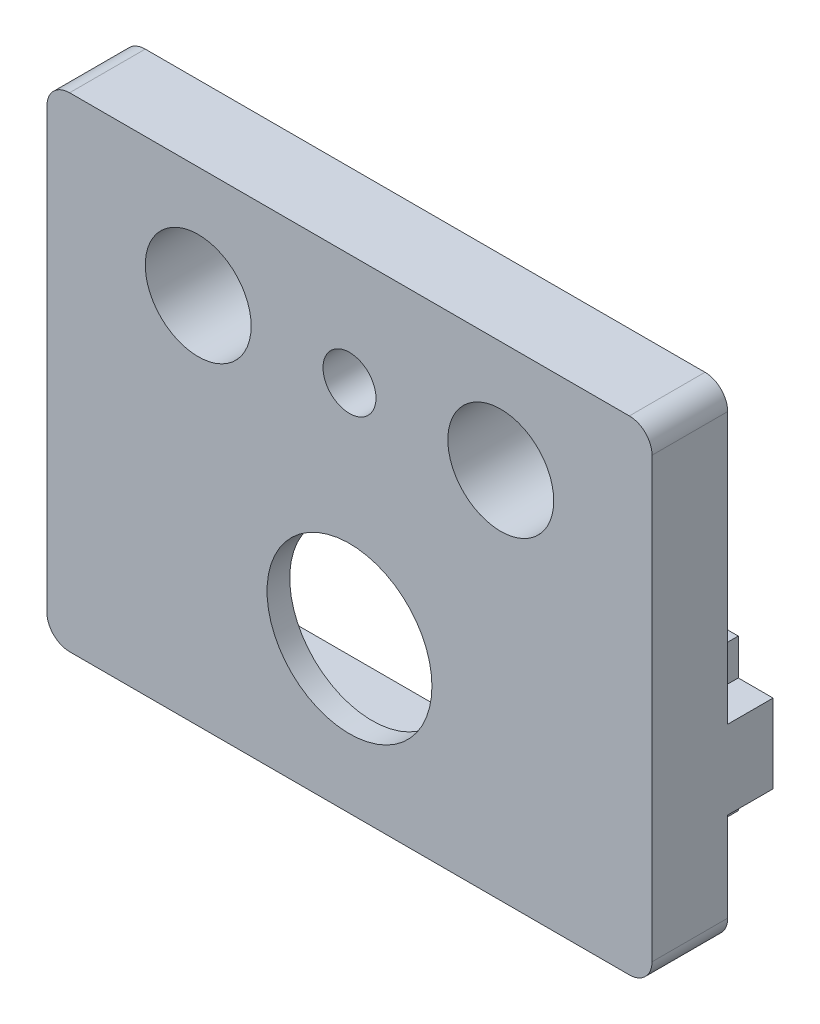
SolidWorks part; units mm, degrees
ref_plane "前视基准面" through (0, 0, 0) normal (0, 0, 1) x (1, 0, 0)
ref_plane "上视基准面" through (0, 0, 0) normal (0, 1, 0) x (1, 0, 0)
ref_plane "右视基准面" through (0, 0, 0) normal (1, 0, 0) x (0, 0, -1)
sketch "草图1" plane through (0, 0, 0) normal (0, 0, 1) x (1, 0, 0)
  line L1 (-9.5, -5.75) -> (9.5, -5.75)
  line L3 (-9.5, 5.75) -> (9.5, 5.75)
  line L5 (-20, -10) -> (20, -10)
  line L6 (-20, -10) -> (-20, 10)
  line L11 (-20, 10) -> (20, 10)
  line L12 (20, -10) -> (20, 10)
  line L13 (-20, -10) -> (20, 10) construction
  line L14 (-20, 10) -> (20, -10) construction
  arc A0 (9.5, -5.75) -> (9.5, 5.75) centre (-0.7708, 0) ccw
  arc A1 (-9.5, -5.75) -> (-9.5, 5.75) centre (0.7708, 0) cw
  point P0 (0, 0)
  point P6 (0, 0)
  point P7 (0, 0)
extrude "凸台-拉伸1" add sketch "草图1" along normal blind 3.5
sketch "草图2" plane through (0, 0, 3.5) normal (0, 0, 1) x (1, 0, 0)
  line L4 (20, -10) -> (20, 10)
  line L5 (20, 10) -> (-20, 10)
  line L6 (-20, 10) -> (-20, -10)
  line L7 (-20, -10) -> (20, -10)
  line L8 (20, -10) -> (20, 10)
  line L9 (20, 10) -> (-20, 10)
  line L10 (-20, 10) -> (-20, -10)
  line L11 (-20, -10) -> (20, -10)
  circle A0 centre (0, 0) radius 5.25
  dimension "D1" = 0
extrude "凸台-拉伸2" add sketch "草图2" along normal blind 1.5
sketch "草图3" plane through (0, 0, 5) normal (0, 0, 1) x (1, 0, 0)
  line L9 (-16.5607, 5.5) -> (-18.2, 5.5)
  line L13 (-13.9, -2.8393) -> (-13.9, 2.8393)
  line L19 (-16.5607, 5.5) -> (-13.9, 2.8393)
  line L22 (-18.2, 3.1) -> (-18.2, 5.5)
  line L23 (-18.2, 3.1) -> (-20, 3.1)
  line L24 (-18.2, -3.1) -> (-20, -3.1)
  line L25 (-18.2, -3.1) -> (-18.2, -5.5)
  line L28 (-16.5607, -5.5) -> (-13.9, -2.8393)
  line L32 (-16.5607, -5.5) -> (-18.2, -5.5)
  line L41 (18.2, 3.1) -> (20, 3.1)
  line L45 (18.2, 3.1) -> (18.2, 5.5)
  line L48 (16.5607, 5.5) -> (13.9, 2.8393)
  line L54 (13.9, -2.8393) -> (13.9, 2.8393)
  line L56 (16.5607, 5.5) -> (18.2, 5.5)
  line L63 (16.5607, -5.5) -> (18.2, -5.5)
  line L67 (16.5607, -5.5) -> (13.9, -2.8393)
  line L70 (18.2, -3.1) -> (18.2, -5.5)
  line L74 (18.2, -3.1) -> (20, -3.1)
  line L88 (-20, 3.1) -> (-20, -3.1)
  line L90 (20, 3.1) -> (20, -3.1)
  point P0 (-10, 0)
  point P8 (-10, 8.2)
  point P9 (-9.8043, 8.2)
  point P13 (-10, 8.2)
  point P20 (-5, 5)
  point P33 (-15, 5)
  point P50 (-15, -5)
  point P51 (-5, -5)
  point P52 (-10, -8.2)
  point P53 (-9.8043, -8.2)
  point P54 (10, 0)
  point P58 (10, 8.2)
  point P59 (10.1957, 8.2)
  point P63 (10, 8.2)
  point P70 (15, 5)
  point P83 (5, 5)
  point P102 (5, -5)
  point P103 (15, -5)
  point P104 (10, -8.2)
  point P105 (10.1957, -8.2)
extrude "凸台-拉伸3" add sketch "草图3" against normal blind 8
sketch "草图4" plane through (0, 0, 5) normal (0, 0, 1) x (1, 0, 0)
  line L3 (-20, 10) -> (-20, -10) construction
  line L6 (20, 10) -> (-20, 10)
  line L8 (-20, 10) -> (-20, 22)
  line L9 (-20, 22) -> (20, 22)
  line L10 (20, 22) -> (20, 10)
  circle A2 centre (-10, 14.64) radius 3.5
  circle A3 centre (10, 14.64) radius 3.5
  line M15 (20, 10) -> (-20, 10)
extrude "凸台-拉伸4" add sketch "草图4" against normal blind 5 contours L10 L9 L8 M15 region at (0, 16.2597, 5)
fillet "圆角1" radius 1.5 4 edges at (-20, 22, 2.5) (20, 22, 2.5) (20, -10, 2.5) (-20, -10, 2.5)
sketch "草图5" plane through (0, 0, 5) normal (0, 0, 1) x (1, 0, 0)
  circle A0 centre (0, 14.64) radius 1.75
extrude "切除-拉伸1" cut sketch "草图5" against normal blind 5
sketch "草图6" plane through (0, 0, -3) normal (0, 0, -1) x (-1, 0, 0)
  line L0 (-18.2, 5.5) -> (-18.2, 3.1) construction
  line L1 (-18.2, 3.1) -> (-20, 3.1) construction
  line L2 (-20, 3.1) -> (-20, -3.1) construction
  line L3 (-20, -3.1) -> (-18.2, -3.1) construction
  line L4 (-18.2, -3.1) -> (-18.2, -5.5) construction
  line L5 (-18.2, -5.5) -> (-16.5607, -5.5) construction
  line L6 (-16.5607, -5.5) -> (-13.9, -2.8393) construction
  line L7 (-13.9, -2.8393) -> (-13.9, 2.8393) construction
  line L8 (-13.9, 2.8393) -> (-16.5607, 5.5) construction
  line L9 (-16.5607, 5.5) -> (-18.2, 5.5) construction
  line L10 (18.2, -5.5) -> (18.2, -3.1) construction
  line L11 (18.2, -3.1) -> (20, -3.1) construction
  line L12 (20, -3.1) -> (20, 3.1) construction
  line L13 (20, 3.1) -> (18.2, 3.1) construction
  line L14 (18.2, 3.1) -> (18.2, 5.5) construction
  line L15 (18.2, 5.5) -> (16.5607, 5.5) construction
  line L16 (16.5607, 5.5) -> (13.9, 2.8393) construction
  line L17 (13.9, 2.8393) -> (13.9, -2.8393) construction
  line L18 (13.9, -2.8393) -> (16.5607, -5.5) construction
  line L19 (16.5607, -5.5) -> (18.2, -5.5) construction
  line L20 (-18.2, 5.5) -> (-18.2, 3.1)
  line L21 (-18.2, 3.1) -> (-20, 3.1)
  line L22 (-20, 3.1) -> (-20, 2.6)
  line L23 (-20, -3.1) -> (-18.2, -3.1)
  line L24 (-18.2, -3.1) -> (-18.2, -5.5)
  line L25 (-18.2, -5.5) -> (-16.5607, -5.5)
  line L26 (-16.5607, -5.5) -> (-13.9, -2.8393)
  line L27 (-13.9, -2.8393) -> (-13.9, 2.8393)
  line L28 (-13.9, 2.8393) -> (-16.5607, 5.5)
  line L29 (-16.5607, 5.5) -> (-18.2, 5.5)
  line L30 (18.2, -5.5) -> (18.2, -3.1)
  line L31 (18.2, -3.1) -> (20, -3.1)
  line L32 (20, -3.1) -> (20, -2.6)
  line L33 (20, 3.1) -> (18.2, 3.1)
  line L34 (18.2, 3.1) -> (18.2, 5.5)
  line L35 (18.2, 5.5) -> (16.5607, 5.5)
  line L36 (16.5607, 5.5) -> (13.9, 2.8393)
  line L37 (13.9, 2.8393) -> (13.9, -2.8393)
  line L38 (13.9, -2.8393) -> (16.5607, -5.5)
  line L39 (16.5607, -5.5) -> (18.2, -5.5)
  line L40 (-20, -2.6) -> (-20, -3.1)
  line L41 (19.5, -2.6) -> (20, -2.6)
  line L42 (19.5, 2.6) -> (20, 2.6)
  line L43 (20, 2.6) -> (20, 3.1)
  line L70 (-17.7, 5) -> (-17.7, 2.6)
  line L71 (-17.7, 2.6) -> (-19.5, 2.6)
  line L72 (-19.5, 2.6) -> (-19.5, -2.6)
  line L73 (-19.5, -2.6) -> (-17.7, -2.6)
  line L74 (-17.7, -2.6) -> (-17.7, -5)
  line L75 (-17.7, -5) -> (-16.7678, -5)
  line L76 (-16.7678, -5) -> (-14.4, -2.6322)
  line L77 (-14.4, -2.6322) -> (-14.4, 2.6322)
  line L78 (-14.4, 2.6322) -> (-16.7678, 5)
  line L79 (-16.7678, 5) -> (-17.7, 5)
  line L80 (-17.7, 5) -> (-17.7, 2.6)
  line L81 (-17.7, 2.6) -> (-19.5, 2.6)
  line L83 (-19.5, -2.6) -> (-17.7, -2.6)
  line L84 (-17.7, -2.6) -> (-17.7, -5)
  line L85 (-17.7, -5) -> (-16.7678, -5)
  line L86 (-16.7678, -5) -> (-14.4, -2.6322)
  line L87 (-14.4, -2.6322) -> (-14.4, 2.6322)
  line L88 (-14.4, 2.6322) -> (-16.7678, 5)
  line L89 (-16.7678, 5) -> (-17.7, 5)
  line L90 (-19.5, -2.6) -> (-20, -2.6)
  line L91 (-19.5, 2.6) -> (-20, 2.6)
  line L100 (17.7, -5) -> (17.7, -2.6)
  line L101 (17.7, -2.6) -> (19.5, -2.6)
  line L102 (19.5, -2.6) -> (19.5, 2.6)
  line L103 (19.5, 2.6) -> (17.7, 2.6)
  line L104 (17.7, 2.6) -> (17.7, 5)
  line L105 (17.7, 5) -> (16.7678, 5)
  line L106 (16.7678, 5) -> (14.4, 2.6322)
  line L107 (14.4, 2.6322) -> (14.4, -2.6322)
  line L108 (14.4, -2.6322) -> (16.7678, -5)
  line L109 (16.7678, -5) -> (17.7, -5)
  line L110 (17.7, -5) -> (17.7, -2.6)
  line L111 (17.7, -2.6) -> (19.5, -2.6)
  line L113 (19.5, 2.6) -> (17.7, 2.6)
  line L114 (17.7, 2.6) -> (17.7, 5)
  line L115 (17.7, 5) -> (16.7678, 5)
  line L116 (16.7678, 5) -> (14.4, 2.6322)
  line L117 (14.4, 2.6322) -> (14.4, -2.6322)
  line L118 (14.4, -2.6322) -> (16.7678, -5)
  line L119 (16.7678, -5) -> (17.7, -5)
  dimension "D1" = 0.5
  dimension "D2" = 0.5
extrude "切除-拉伸2" cut sketch "草图6" against normal blind 3
sketch "草图7" plane through (0, 0, 0) normal (0, 0, -1) x (-1, 0, 0)
  line L4 (9.6166, 5.95) -> (-9.6166, 5.95)
  line L5 (-9.6166, -5.95) -> (9.6166, -5.95)
  line L6 (9.6166, 5.95) -> (-9.6166, 5.95)
  line L7 (-9.6166, -5.95) -> (9.6166, -5.95)
  arc A4 (9.6166, -5.95) -> (9.6166, 5.95) centre (-0.7708, 0) ccw
  arc A5 (-9.6166, 5.95) -> (-9.6166, -5.95) centre (0.7708, 0) ccw
  arc A6 (9.6166, -5.95) -> (9.6166, 5.95) centre (-0.7708, 0) ccw
  arc A7 (-9.6166, 5.95) -> (-9.6166, -5.95) centre (0.7708, 0) ccw
  dimension "D1" = 0.2
extrude "切除-拉伸3" cut sketch "草图7" against normal blind 3.5
sketch "草图8" plane through (0, 0, 5) normal (0, 0, 1) x (1, 0, 0)
  circle A0 centre (0, 0) radius 5.25 construction
  circle A1 centre (0, 0) radius 5.25
  circle A2 centre (0, 0) radius 5.45
  dimension "D1" = 0.2
extrude "切除-拉伸4" cut sketch "草图8" against normal blind 3.5
